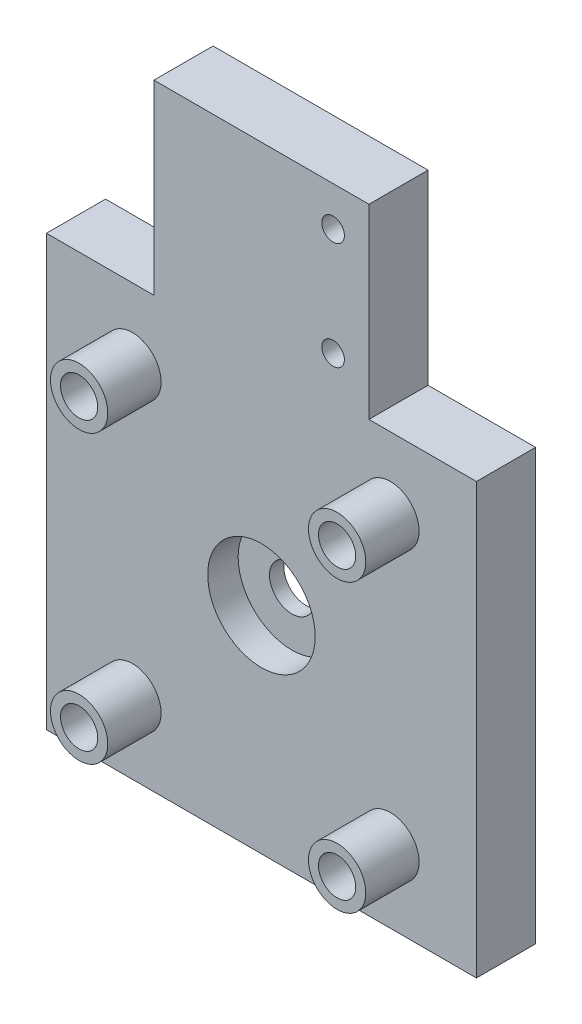
SolidWorks part; units mm, degrees
ref_plane "Front Plane" through (0, 0, 0) normal (0, 0, 1) x (1, 0, 0)
ref_plane "Top Plane" through (0, 0, 0) normal (0, 1, 0) x (1, 0, 0)
ref_plane "Right Plane" through (0, 0, 0) normal (1, 0, 0) x (0, 0, -1)
sketch "Sketch1" plane through (0, 0, 0) normal (0, 0, 1) x (1, 0, 0)
  line L1 (-19.05, -38.1) -> (19.05, -38.1)
  line L2 (-19.05, -38.1) -> (-19.05, 38.1)
  line L3 (-19.05, 38.1) -> (19.05, 38.1)
  line L4 (19.05, -38.1) -> (19.05, 38.1)
  line L5 (-19.05, -38.1) -> (19.05, 38.1) construction
  line L6 (-19.05, 38.1) -> (19.05, -38.1) construction
  point P0 (0, 0)
  dimension "D1" = 38.1
  dimension "D2" = 76.2
extrude "Boss-Extrude1" add sketch "Sketch1" along normal blind 7.9375
sketch "Sketch2" plane through (0, 0, 7.9375) normal (0, 0, 1) x (1, 0, 0)
  circle A0 centre (0, 0) radius 3.9688
  dimension "D1" = 7.9375
extrude "Cut-Extrude1" cut sketch "Sketch2" against normal through all
sketch "Sketch4" plane through (0, 0, 7.9375) normal (0, 0, 1) x (1, 0, 0)
  circle A0 centre (0, 0) radius 9.525
  dimension "D1" = 19.05
extrude "Cut-Extrude2" cut sketch "Sketch4" against normal offset from surface (5.3975 mm away) 2.54 up to face at (3.9688, 0, 0)
sketch "Sketch8" plane through (0, 0, 7.9375) normal (0, 0, 1) x (1, 0, 0)
  line L0 (-19.05, -38.1) -> (19.05, -38.1) construction
  line L1 (-19.05, 38.1) -> (-38.1, 38.1)
  line L2 (-19.05, 38.1) -> (-19.05, -38.1)
  line L3 (-19.05, -38.1) -> (-38.1, -38.1)
  line L4 (-38.1, 38.1) -> (-38.1, -38.1)
  line L5 (0, 38.1) -> (0, -38.1) construction
  line L6 (19.05, 38.1) -> (-19.05, 38.1) construction
  line L7 (19.05, -38.1) -> (38.1, -38.1)
  line L8 (38.1, 38.1) -> (38.1, -38.1)
  line L9 (19.05, 38.1) -> (38.1, 38.1)
  line L10 (19.05, 38.1) -> (19.05, -38.1)
  dimension "D1" = 38.1
extrude "Boss-Extrude5" add sketch "Sketch8" against normal up to surface (7.9375 mm away) up to face at (3.9688, 0, 0)
sketch "Sketch5" plane through (0, 0, 7.9375) normal (0, 0, 1) x (1, 0, 0)
  line L0 (38.1, 38.1) -> (-38.1, 38.1) construction
  line L1 (0, 38.1) -> (0, -38.1) construction
  line L2 (38.1, 38.1) -> (-38.1, 38.1) construction
  line L3 (-38.1, -38.1) -> (38.1, -38.1) construction
  circle A0 centre (22.86, 25.4) radius 5.08
  circle A1 centre (-22.86, 25.4) radius 5.08
  dimension "D1" = 10.16
  dimension "D2" = 12.7
  dimension "D3" = 22.86
extrude "Boss-Extrude2" add sketch "Sketch5" along normal blind 9.4488
sketch "Sketch6" plane through (0, 0, 17.3863) normal (0, 0, 1) x (1, 0, 0)
  line L0 (0, 38.1) -> (0, -38.1) construction
  line L1 (38.1, 38.1) -> (-38.1, 38.1) construction
  line L2 (-38.1, -38.1) -> (38.1, -38.1) construction
  circle A0 centre (22.86, 25.4) radius 3.302
  circle A1 centre (-22.86, 25.4) radius 3.302
  dimension "D1" = 6.604
extrude "Cut-Extrude3" cut sketch "Sketch6" against normal through all
mirror "Mirror1" about plane through (0, 0, 0) normal (0, 1, 0) of "Cut-Extrude3", "Boss-Extrude2"
sketch "Sketch7" plane through (0, 0, 7.9375) normal (0, 0, 1) x (1, 0, 0)
  line L1 (-19.05, 38.1) -> (19.05, 38.1)
  line L2 (-19.05, 38.1) -> (-19.05, 71.12)
  line L3 (-19.05, 71.12) -> (19.05, 71.12)
  line L4 (19.05, 38.1) -> (19.05, 71.12)
  line L5 (-19.05, 54.61) -> (19.05, 54.61) construction
  line L6 (12.7, 71.12) -> (12.7, 38.1) construction
  line L7 (38.1, 38.1) -> (-38.1, 38.1) construction
  line L8 (0, 71.12) -> (0, -38.1) construction
  line L9 (-38.1, -38.1) -> (38.1, -38.1) construction
  circle A0 centre (12.7, 64.135) radius 2
  circle A1 centre (12.7, 45.085) radius 2
  dimension "D4" = 4
  dimension "D1" = 33.02
  dimension "D2" = 9.525
  dimension "D3" = 6.35
  dimension "D5" = 38.1
extrude "Boss-Extrude4" add sketch "Sketch7" against normal up to surface (7.9375 mm away) up to face at (26.162, -25.4, 0)
sketch "Sketch9" plane through (0, 0, 0) normal (0, 0, -1) x (-1, 0, 0)
  line L1 (-12.7, -12.7) -> (12.7, -12.7)
  line L2 (-12.7, -12.7) -> (-12.7, 12.7)
  line L3 (-12.7, 12.7) -> (12.7, 12.7)
  line L4 (12.7, -12.7) -> (12.7, 12.7)
  line L5 (-12.7, -12.7) -> (12.7, 12.7) construction
  line L6 (-12.7, 12.7) -> (12.7, -12.7) construction
  line L14 (-19.05, 38.1) -> (-38.1, 38.1)
  line L15 (-38.1, 38.1) -> (-38.1, -38.1)
  line L16 (-38.1, -38.1) -> (38.1, -38.1)
  line L17 (38.1, -38.1) -> (38.1, 38.1)
  line L18 (38.1, 38.1) -> (19.05, 38.1)
  line L19 (19.05, 38.1) -> (19.05, 71.12)
  line L20 (19.05, 71.12) -> (-19.05, 71.12)
  line L21 (-19.05, 71.12) -> (-19.05, 38.1)
  line L22 (-19.05, 38.1) -> (-38.1, 38.1)
  line L23 (-38.1, 38.1) -> (-38.1, -38.1)
  line L24 (-38.1, -38.1) -> (38.1, -38.1)
  line L25 (38.1, -38.1) -> (38.1, 38.1)
  line L26 (38.1, 38.1) -> (19.05, 38.1)
  line L27 (19.05, 38.1) -> (19.05, 71.12)
  line L28 (19.05, 71.12) -> (-19.05, 71.12)
  line L29 (-19.05, 71.12) -> (-19.05, 38.1)
  circle A1 centre (22.86, 25.4) radius 3.302
  circle A2 centre (22.86, 25.4) radius 3.302
  circle A3 centre (-22.86, 25.4) radius 3.302
  circle A4 centre (-22.86, 25.4) radius 3.302
  circle A5 centre (22.86, -25.4) radius 3.302
  circle A6 centre (22.86, -25.4) radius 3.302
  circle A7 centre (-22.86, -25.4) radius 3.302
  circle A8 centre (-22.86, -25.4) radius 3.302
  circle A9 centre (-12.7, 45.085) radius 2
  circle A10 centre (-12.7, 45.085) radius 2
  circle A11 centre (-12.7, 64.135) radius 2
  circle A12 centre (-12.7, 64.135) radius 2
  point P0 (0, 0)
  dimension "D7" = 25.4
  dimension "D8" = 25.4
  dimension "D1" = 0
  dimension "D2" = 0
  dimension "D3" = 0
  dimension "D4" = 0
  dimension "D5" = 0
  dimension "D6" = 0
  dimension "D9" = 0
extrude "Boss-Extrude6" add sketch "Sketch9" along normal blind 2.54 contours L22 L23 L24 L25 L26 L27 L28 L29 | A10 | A12 | A4 | L2 L1 L4 L3 | A8 | A6 | A2
